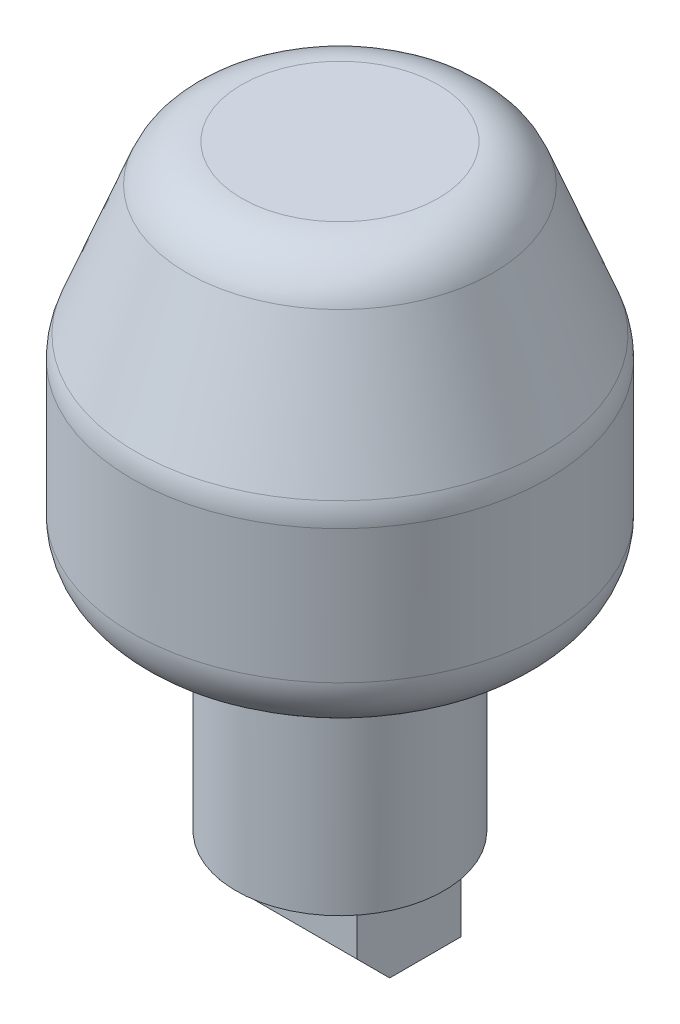
SolidWorks part; units mm, degrees
ref_plane "Front Plane" through (0, 0, 0) normal (0, 0, 1) x (1, 0, 0)
ref_plane "Top Plane" through (0, 0, 0) normal (0, 1, 0) x (1, 0, 0)
ref_plane "Right Plane" through (0, 0, 0) normal (1, 0, 0) x (0, 0, -1)
sketch "Sketch1" plane through (0, 0, 0) normal (0, 0, 1) x (1, 0, 0)
  line L0 (0, 0) -> (11.2395, 0)
  line L1 (11.2395, 0) -> (11.2395, 23.4188)
  line L2 (11.2395, 23.4188) -> (22.4734, 23.4188)
  line L3 (22.4734, 23.4188) -> (22.4734, 45.4152)
  line L4 (22.4734, 45.4152) -> (14.986, 64.6193)
  line L5 (14.986, 64.6193) -> (0, 64.6193)
  line L6 (0, 64.6193) -> (0, 0) construction
  line L7 (0, 0) -> (0, 64.6193)
  dimension "D1" = 22.479
  dimension "D2" = 23.4188
  dimension "D3" = 21.9964
  dimension "D4" = 111.3
  dimension "D5" = 20.6121
  dimension "D6" = 14.986
revolve "Revolve1" add sketch "Sketch1" angle 360 about L6
fillet "Fillet2" radius 6.35 3 edges at (-22.4734, 23.4188, 0) (-22.4734, 45.4152, 0) (-14.986, 64.6193, 0)
sketch "Sketch2" plane through (0, 0, 0) normal (1, 0, 0) x (0, 0, -1)
  line L0 (-11.2395, 0) -> (11.2395, 0) construction
  line L1 (-5.6262, 0) -> (5.6262, 0)
  line L2 (-5.6262, -5.461) -> (-2.07, -9.0172)
  line L3 (5.6262, 0) -> (-5.6262, 0)
  line L4 (5.6262, 0) -> (5.6262, -9.0172)
  line L5 (5.6262, -9.0172) -> (-2.07, -9.0172)
  line L6 (-5.6262, 0) -> (-5.6262, -5.461)
  point P3 (0, 0)
  dimension "D1" = 5.461
  dimension "D2" = 5.0292
  dimension "D3" = 135
  dimension "D4" = 7.6962
extrude "Boss-Extrude1" add sketch "Sketch2" along normal mid plane 14.9098 contours L1 L6 L2 L5 L4 region at (0, -4.2877, -0.2951)
sketch "Sketch3" plane through (0, -9.0172, 0) normal (0, -1, 0) x (1, 0, 0)
  line L4 (-2.5476, 1.943) -> (-2.5476, -5.4992)
  line L5 (-2.4206, 1.943) -> (-2.4206, -5.4992)
  line L6 (2.5476, 1.943) -> (2.5476, -5.4992)
  line L7 (2.4206, 1.943) -> (2.4206, -5.4992)
  line L8 (-7.3279, 1.943) -> (-7.3279, -5.4992)
  line L9 (-7.3279, -5.4992) -> (7.3279, -5.4992)
  line L10 (7.3279, -5.4992) -> (7.3279, 1.943)
  line L11 (7.3279, 1.943) -> (-7.3279, 1.943)
  line L12 (-7.3279, 1.943) -> (-7.3279, -5.4992)
  line L13 (-7.3279, -5.4992) -> (7.3279, -5.4992)
  line L14 (7.3279, -5.4992) -> (7.3279, 1.943)
  line L15 (7.3279, 1.943) -> (-7.3279, 1.943)
  dimension "D2" = 0.127
  dimension "D3" = 0.127
  dimension "D4" = 4.7803
  dimension "D5" = 4.7803
  dimension "D1" = 0.127
extrude "Cut-Extrude1" cut sketch "Sketch3" against normal blind 2.54 contours L4 L15 L12 L13 | L7 L15 L5 L13 | L14 L15 L6 L13 region at (-4.9378, -9.0172, -1.7781) region at (0, -9.0172, -1.7781) region at (4.9378, -9.0172, -1.7781)
sketch "Sketch4" plane through (0, 0, 0) normal (0, 0, 1) x (1, 0, 0)
  line L1 (-11.2395, 23.4188) -> (11.2395, 23.4188) construction
  line L3 (-1.778, 21.2344) -> (1.778, 21.2344)
  line L4 (-1.778, 21.2344) -> (-1.778, 23.4188)
  line L5 (-1.778, 23.4188) -> (1.778, 23.4188)
  line L6 (1.778, 21.2344) -> (1.778, 23.4188)
  line L7 (-1.778, 21.2344) -> (1.778, 23.4188) construction
  line L8 (-1.778, 23.4188) -> (1.778, 21.2344) construction
  point P0 (0, 22.3266)
  dimension "D1" = 3.556
  dimension "D2" = 2.1844
extrude "Boss-Extrude2" add sketch "Sketch4" against normal up to surface (3.1971 mm away) from offset 14.2951 up to face at (-11.2395, 23.4188, 0)
sketch "Sketch5" plane through (0, -6.4772, 0) normal (0, -1, 0) x (-1, 0, 0)
  line L0 (7.4549, 5.6262) -> (2.5476, -1.943) construction
  line L1 (2.4206, 5.4992) -> (-2.4206, -1.943) construction
  line L2 (-2.4206, -1.943) -> (2.4206, -1.943) construction
  line L3 (-2.4206, -1.943) -> (-2.4206, 5.4992) construction
  line L4 (-2.5476, 5.4992) -> (-7.3279, -1.943) construction
  point P0 (-4.9378, 1.7781)
  point P1 (0, 1.7781)
  point P2 (5.0013, 1.8416)
sketch "0_0_Point" plane through (0, -6.4772, 0) normal (0, -1, 0) x (1, 0, 0)
  point P0 (4.9378, -1.7781)
other "0_0" parameters "Diameter"=2, "StubLength"=2
ref_axis "Axis1" through (4.9378, -16.4772, -1.7781) along (0, 1, 0)
sketch "0_1_Point" plane through (0, -6.4772, 0) normal (0, -1, 0) x (1, 0, 0)
  point P0 (-4.9378, -1.7781)
other "0_1" parameters "Diameter"=2, "StubLength"=2
ref_axis "Axis2" through (-4.9378, -16.4772, -1.7781) along (0, 1, 0)
sketch "0_2_Point" plane through (0, -6.4772, 0) normal (0, -1, 0) x (1, 0, 0)
  point P0 (0, -1.7781)
other "0_2" parameters "Diameter"=2, "StubLength"=2
ref_axis "Axis3" through (0, -16.4772, -1.7781) along (0, 1, 0)
